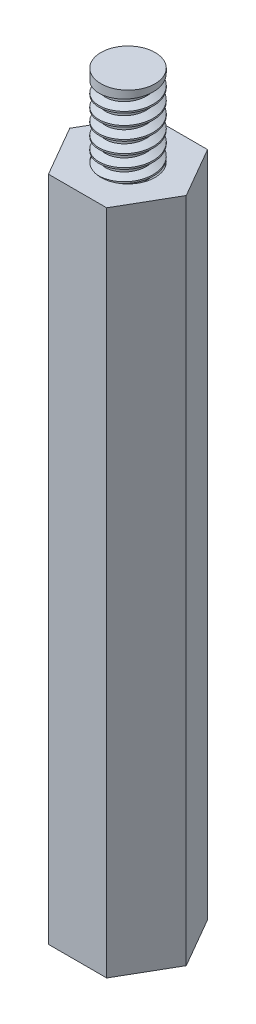
SolidWorks part; units mm, degrees
material "1060 Alloy"
ref_plane "Front Plane" through (0, 0, 0) normal (0, 0, 1) x (1, 0, 0)
ref_plane "Top Plane" through (0, 0, 0) normal (0, 1, 0) x (1, 0, 0)
ref_plane "Right Plane" through (0, 0, 0) normal (1, 0, 0) x (0, 0, -1)
sketch "Sketch1" plane through (0, 0, 0) normal (0, 1, 0) x (1, 0, 0)
  line L1 (2.1515, 0) -> (1.0758, 1.8633)
  line L2 (1.0758, 1.8633) -> (-1.0758, 1.8633)
  line L3 (-1.0758, 1.8633) -> (-2.1515, 0)
  line L4 (-2.1515, 0) -> (-1.0758, -1.8633)
  line L5 (-1.0758, -1.8633) -> (1.0758, -1.8633)
  line L6 (1.0758, -1.8633) -> (2.1515, 0)
  circle A0 centre (0, 0) radius 1
  circle A1 centre (0, 0) radius 1.8633 construction
extrude "Boss-Extrude1" add sketch "Sketch1" along normal blind 24.638 contours L5 L6 L1 L2 L3 L4 A0 | A0 region at (1.5643, 0, 0.9032) region at (0, 0, 0)
extrude "Cut-Extrude1" cut sketch "Sketch1<3>" along normal blind 5 contours A0 region at (0, 0, 0)
sketch "Sketch1<3>" plane through (0, 0, 0) normal (0, 1, 0) x (1, 0, 0) same geometry as "Sketch1"
sketch "Sketch2" plane through (0, 24.638, 0) normal (0, 1, 0) x (1, 0, 0)
  circle A0 centre (0, 0) radius 1
extrude "Boss-Extrude2" add sketch "Sketch2" along normal blind 3 and the other way blind 1
thread "Thread1" pitch 0.45 method cut profile "Thread Profile1" start angle 0, offset 0, length 0, pitch 0.45, diameter 2
ref_plane "Plane1" through (-1, 27.638, 0) normal (0, 0, 1) x (-1, 0, 0)
sketch "Thread Profile1" plane through (-1, 27.638, 0) normal (0, 0, 1) x (-1, 0, 0)
  line L0 (0, 0) -> (0, 0.45) construction
  line L11 (0, 0) -> (0, 0.3937)
  line L12 (0, 0.3937) -> (-0.2436, 0.2531)
  line L13 (-0.2436, 0.2531) -> (-0.2436, 0.1406)
  line L15 (-0.2436, 0.1406) -> (0, 0)
  line L17 (-0.2436, 0.1969) -> (0, 0.1969) construction
  point P2 (0, 0)
  dimension "Pitch" = 0.45
  dimension "Profile_Angle" = 60
  dimension "Profile_Land" = 0.1125
  dimension "Profile_Height" = 0.2436
thread "Thread2" pitch 0.45 method extrude profile "Thread Profile2" start angle 0, offset 0, length 2, pitch 0.45, diameter 2
ref_plane "Plane2" through (1, 0, 0) normal (0, 0, 1) x (1, 0, 0)
sketch "Thread Profile2" plane through (1, 0, 0) normal (0, 0, 1) x (1, 0, 0)
  line L0 (0, 0) -> (0, 0.45) construction
  line L11 (0, 0) -> (0, 0.3937)
  line L12 (0, 0.3937) -> (-0.2436, 0.2531)
  line L13 (-0.2436, 0.2531) -> (-0.2436, 0.1406)
  line L15 (-0.2436, 0.1406) -> (0, 0)
  line L17 (-0.2436, 0.1969) -> (0, 0.1969) construction
  point P2 (0, 0)
  dimension "Pitch" = 0.45
  dimension "Profile_Angle" = 60
  dimension "Profile_Land" = 0.1125
  dimension "Profile_Height" = 0.2436
